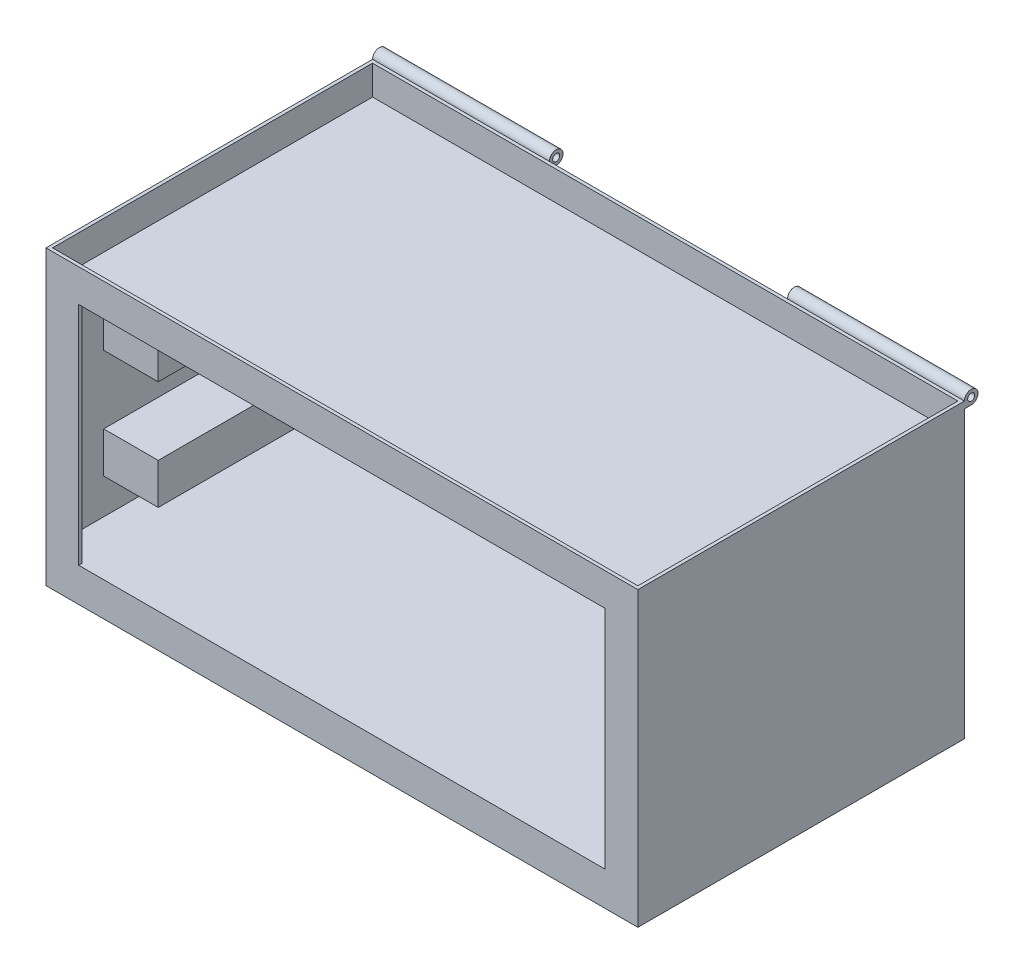
SolidWorks part; units mm, degrees
note: The reader was unsure of these and kept them because the rebuilt part matched: shared geometry of "Sketch1<13>", "Sketch1<14>", "Sketch1<15>".
material "AISI 4130 Steel, normalized at 870C"
ref_plane "Front Plane" through (0, 0, 0) normal (0, 0, 1) x (1, 0, 0)
ref_plane "Top Plane" through (0, 0, 0) normal (0, 1, 0) x (1, 0, 0)
ref_plane "Right Plane" through (0, 0, 0) normal (1, 0, 0) x (0, 0, -1)
sketch "Sketch1" plane through (0, 0, 0) normal (0, 1, 0) x (1, 0, 0)
  line L0 (0, 0) -> (-1.524, 0) construction
  line L9 (0, 0) -> (273.177, 0)
  line L10 (0, 0) -> (0, 149.352)
  line L11 (0, 149.352) -> (273.177, 149.352)
  line L12 (273.177, 0) -> (273.177, 149.352)
  line L13 (-1.524, -1.524) -> (274.701, -1.524)
  line L14 (-1.524, -1.524) -> (-1.524, 150.876)
  line L15 (-1.524, 150.876) -> (274.701, 150.876)
  line L16 (274.701, -1.524) -> (274.701, 150.876)
  line L17 (0, 149.352) -> (0, 150.876) construction
  line L18 (273.177, 149.352) -> (274.701, 149.352) construction
  line L19 (273.177, 0) -> (273.177, -1.524) construction
  line L20 (13.716, 0) -> (13.716, -1.524)
  line L21 (136.5885, 150.876) -> (136.5885, -1.524) construction
  line L22 (259.461, 0) -> (259.461, -1.524)
  dimension "D1" = 1.524
  dimension "D2" = 276.225
  dimension "D3" = 152.4
  dimension "D4" = 15.24
extrude "Bulk-Extrude" add sketch "Sketch1" against normal blind 136.525 contours L14 L13 L16 L15
extrude "Inner Shell-Cut" cut sketch "Sketch1<13>" against normal offset from surface (120.65 mm away) 15.875 contours L9 L12 L11 L10 | L22 L9 L20 L13 up to face at (136.5885, -136.525, -74.676)
sketch "Sketch1<13>" plane through (0, 0, 0) normal (0, 1, 0) x (1, 0, 0) same geometry as "Sketch1"
extrude "Top Wall-Extrude" add sketch "Sketch1<14>" against normal blind 15.24 contours L22 L9 L20 L13
sketch "Sketch1<14>" plane through (0, 0, 0) normal (0, 1, 0) x (1, 0, 0) same geometry as "Sketch1"
extrude "Top Floor-Extrude" add sketch "Sketch1<15>" along normal blind 1.524 from surface at -15.24 contours L9 L12 L11 L10 starting at face at (136.5885, -15.24, 0.762)
sketch "Sketch1<15>" plane through (0, 0, 0) normal (0, 1, 0) x (1, 0, 0) same geometry as "Sketch1"
ref_plane "Mid Plane" through (136.5885, 0, 0) normal (1, 0, 0) x (0, 0, -1)
sketch "Sketch5" plane through (274.701, 0, 0) normal (1, 0, 0) x (0, 0, -1)
  line L0 (150.876, 0) -> (154.051, 0)
  line L2 (154.051, -3.175) -> (150.876, -3.175)
  line L3 (150.876, -136.525) -> (150.876, 0) construction
  circle A0 centre (154.051, 0) radius 3.175
  circle A1 centre (154.051, 0) radius 1.651
  dimension "D1" = 1.524
  dimension "D2" = 6.35
extrude "Hinge-Extrude" add sketch "Sketch5" against normal blind 82.55
mirror "Mirror1" about plane through (136.5885, 0, 0) normal (1, 0, 0) of "Hinge-Extrude"
sketch "Sketch7" plane through (0, 0, -149.352) normal (0, 0, 1) x (1, 0, 0)
  line L0 (273.177, -120.65) -> (273.177, -15.24) construction
  line L1 (0, -34.29) -> (25.4635, -34.29)
  line L2 (0, -34.29) -> (0, -53.34)
  line L3 (0, -53.34) -> (25.4635, -53.34)
  line L4 (25.4635, -34.29) -> (25.4635, -53.34)
  line L5 (273.177, -34.29) -> (247.7135, -34.29)
  line L6 (273.177, -34.29) -> (273.177, -53.34)
  line L7 (273.177, -53.34) -> (247.7135, -53.34)
  line L8 (247.7135, -34.29) -> (247.7135, -53.34)
  line L9 (0, -120.65) -> (0, -15.24) construction
  line L10 (0, -85.09) -> (25.4635, -85.09)
  line L11 (0, -85.09) -> (0, -104.14)
  line L12 (0, -104.14) -> (25.4635, -104.14)
  line L13 (25.4635, -85.09) -> (25.4635, -104.14)
  line L14 (0, -15.24) -> (0, -34.29) construction
  line L15 (273.177, -85.09) -> (247.7135, -85.09)
  line L16 (273.177, -85.09) -> (273.177, -104.14)
  line L17 (273.177, -104.14) -> (247.7135, -104.14)
  line L18 (247.7135, -85.09) -> (247.7135, -104.14)
  line L19 (0, -15.24) -> (273.177, -15.24) construction
  line L20 (273.177, -15.24) -> (273.177, -34.29) construction
  line L21 (0, -53.34) -> (0, -85.09) construction
  line L22 (273.177, -53.34) -> (273.177, -85.09) construction
  dimension "D1" = 19.05
  dimension "D2" = 31.75
  dimension "D3" = 19.05
  dimension "D4" = 222.25
extrude "Rails-Extrude" add sketch "Sketch7" along normal offset from surface (125.476 mm away) 25.4 up to face at (136.5885, -68.2625, 1.524)
